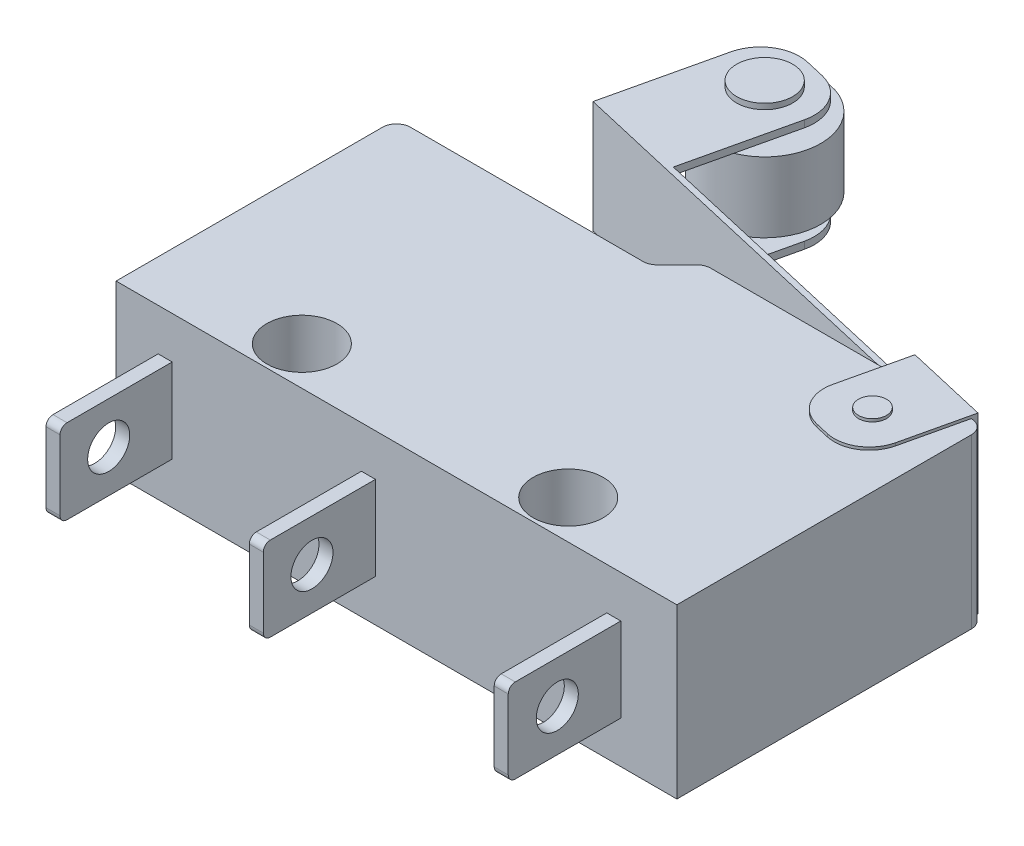
SolidWorks part; units mm, degrees
ref_plane "Ön Düzlem" through (0, 0, 0) normal (0, 0, 1) x (1, 0, 0)
ref_plane "Üst Düzlem" through (0, 0, 0) normal (0, 1, 0) x (1, 0, 0)
ref_plane "Sağ Düzlem" through (0, 0, 0) normal (1, 0, 0) x (0, 0, -1)
sketch "Çizim1" plane through (0, 0, 0) normal (0, 1, 0) x (1, 0, 0)
  line L0 (-10, 4.5) -> (10, 4.5) construction
  line L1 (0.2071, 5.5) -> (9.5, 5.5)
  line L2 (-10, 4) -> (-10, -5.5)
  line L3 (-10, -5.5) -> (10, -5.5)
  line L4 (10, 5) -> (10, -5.5)
  line L5 (-10, 5.5) -> (10, -5.5) construction
  line L6 (-10, -5.5) -> (10, 5.5) construction
  line L7 (0, 5.5) -> (0, -5.5) construction
  line L8 (-9.5, 4.5) -> (-1.2071, 4.5)
  line L9 (-0.8536, 4.6464) -> (-0.1464, 5.3536)
  line L10 (-10, -4.125) -> (10, -4.125) construction
  circle A0 centre (-4.75, -4.125) radius 1.25
  circle A1 centre (4.75, -4.125) radius 1.25
  arc A2 (9.5, 5.5) -> (10, 5) centre (9.5, 5) cw
  arc A3 (0.2071, 5.5) -> (-0.1464, 5.3536) centre (0.2071, 5) ccw
  arc A4 (-1.2071, 4.5) -> (-0.8536, 4.6464) centre (-1.2071, 5) ccw
  arc A5 (-10, 4) -> (-9.5, 4.5) centre (-9.5, 4) cw
  point P0 (0, 0)
  point P25 (-1, 4.5)
  dimension "D6" = 2.5
  dimension "D7" = 5.25
  dimension "D8" = 0.5
  dimension "D1" = 20
  dimension "D2" = 11
  dimension "D3" = 10
  dimension "D4" = 45
  dimension "D5" = 2.75
extrude "Yükseklik-Ekstrüzyon1" add sketch "Çizim1" along normal blind 3 and the other way blind 3
sketch "Çizim2" plane through (0, 0, -5.5) normal (0, 0, -1) x (-1, 0, 0)
  line L0 (-1.8536, 3) -> (-1.8536, -3) construction
  line L1 (-9.5, 3) -> (-0.2071, 3) construction
  line L2 (-9.5, -3) -> (-0.2071, -3) construction
  line L3 (0.1464, -3) -> (0.1464, 3) construction
  line L4 (-2.8536, 1) -> (-0.8536, 1)
  line L5 (-2.8536, 1) -> (-2.8536, -1)
  line L6 (-2.8536, -1) -> (-0.8536, -1)
  line L7 (-0.8536, 1) -> (-0.8536, -1)
  line L8 (-2.8536, 1) -> (-0.8536, -1) construction
  line L9 (-2.8536, -1) -> (-0.8536, 1) construction
  point P6 (-1.8536, 0)
  dimension "D1" = 2
  dimension "D2" = 2
  dimension "D3" = 2
extrude "Yükseklik-Ekstrüzyon2" add sketch "Çizim2" along normal blind 1.5
ref_plane "Düzlem1" through (0, 0, 0) normal (0, 1, 0) x (1, 0, 0)
sketch "Çizim3" plane through (0, 0, 0) normal (0, 1, 0) x (1, 0, 0)
  line L0 (9.5, 5.5) -> (-8.0387, 9.5491) construction
  line L10 (9.5, 5.5) -> (8.9939, 3.3077)
  line L11 (7.4947, 2.3709) -> (7.0075, 2.4834)
  line L12 (6.0707, 3.9825) -> (6.5769, 6.1749)
  line L13 (6.5769, 6.1749) -> (-8.0387, 9.5491)
  line L14 (-8.0387, 9.5491) -> (-7.1164, 13.544)
  line L15 (-5.4373, 14.5932) -> (-4.7553, 14.4358)
  line L16 (-3.7061, 12.7567) -> (-4.5834, 8.9567)
  line L17 (-4.5834, 8.9567) -> (9.545, 5.6949)
  line L19 (9.5, 5.5) -> (9.545, 5.6949)
  line L20 (9.5, 5.5) -> (0.2071, 5.5) construction
  arc A2 (-4.7553, 14.4358) -> (-3.7061, 12.7567) centre (-5.0702, 13.0716) cw
  arc A3 (-7.1164, 13.544) -> (-5.4373, 14.5932) centre (-5.7522, 13.2291) cw
  arc A4 (8.9939, 3.3077) -> (7.4947, 2.3709) centre (7.7759, 3.5889) cw
  arc A5 (7.0075, 2.4834) -> (6.0707, 3.9825) centre (7.2887, 3.7013) cw
  point P12 (-3.3911, 14.1208)
  point P15 (-6.8014, 14.9082)
  point P18 (8.7127, 2.0897)
  point P22 (5.7896, 2.7646)
  dimension "D6" = 5.5
  dimension "D10" = 1.4
  dimension "D11" = 1.25
  dimension "D1" = 18
  dimension "D2" = 90
  dimension "D3" = 3.5
  dimension "D4" = 3
  dimension "D5" = 90
  dimension "D7" = 3.5
  dimension "D8" = 90
  dimension "D9" = 5.3
  dimension "D12" = 13
extrude "Yükseklik-Ekstrüzyon6" add sketch "Çizim3" along normal blind 3.1 and the other way blind 3.1
sketch "Çizim4" plane through (1.7312, 0, -7.4988) normal (0.225, 0, -0.9744) x (-0.9744, 0, -0.225)
  line L0 (-5.0193, 3.1) -> (-5.0193, -3.1) construction
  line L1 (-5.0193, 2.5006) -> (-4.5193, 2.0006)
  line L2 (-8.0193, -3.1) -> (6.4807, -3.1) construction
  line L3 (-8.0193, -3.1) -> (-8.0193, 3.1) construction
  line L4 (-5.0193, 0) -> (6.4807, 0) construction
  line L5 (6.4807, -3.1) -> (6.4807, 3.1) construction
  line L6 (-5.0193, 3.1) -> (10.02, 3.1)
  line L7 (-5.0193, 3.1) -> (-5.0193, 2.5006)
  line L8 (-4.5193, 2.0006) -> (10.02, 2.0006)
  line L9 (10.02, 3.1) -> (10.02, 2.0006)
  line L10 (-4.5193, -2.0006) -> (10.02, -2.0006)
  line L11 (10.02, -3.1) -> (10.02, -2.0006)
  line L12 (-5.0193, -3.1) -> (10.02, -3.1)
  line L13 (-5.0193, -2.5006) -> (-4.5193, -2.0006)
  line L14 (-5.0193, -3.1) -> (-5.0193, -2.5006)
  point P2 (-5.0193, 2.0006)
  point P13 (-5.0193, 2.6)
  dimension "D1" = 3
  dimension "D2" = 1.0994
  dimension "D5" = 0.5
extrude "Kes-Ekstrüzyon1" cut sketch "Çizim4" against normal blind 0.5 and the other way blind 6
sketch "Çizim5" plane through (2.9235, 0, -12.663) normal (0.225, 0, -0.9744) x (-0.9744, 0, -0.225)
  line L0 (8.2307, 2.0006) -> (8.2307, -2.0006) construction
  line L1 (8.5807, 2.0006) -> (7.8807, 2.0006) construction
  line L2 (7.8807, -2.0006) -> (8.5807, -2.0006) construction
  line L3 (9.9807, 2.0006) -> (8.5807, 2.0006) construction
  line L4 (5.7307, 1.7506) -> (10.7307, 1.7506)
  line L5 (5.7307, 1.7506) -> (5.7307, -1.7506)
  line L6 (5.7307, -1.7506) -> (10.7307, -1.7506)
  line L7 (10.7307, 1.7506) -> (10.7307, -1.7506)
  line L8 (5.7307, 1.7506) -> (10.7307, -1.7506) construction
  line L9 (5.7307, -1.7506) -> (10.7307, 1.7506) construction
  point P6 (8.2307, 0)
  dimension "D1" = 0.25
  dimension "D2" = 5
extrude "Kes-Ekstrüzyon2" cut sketch "Çizim5" against normal blind 5.25
ref_plane "Düzlem2" through (0, 0.0006, 0) normal (0, 1, 0) x (1, 0, 0)
sketch "Çizim6" plane through (0, 0.0006, 0) normal (0, 1, 0) x (1, 0, 0)
  line L0 (-5.0963, 14.5145) -> (-6.3335, 9.1555) construction
  line L1 (-5.4373, 14.5932) -> (-4.7553, 14.4358) construction
  line L2 (6.0897, 6.2873) -> (-8.0387, 9.5491) construction
  circle A0 centre (-5.4313, 13.0633) radius 2
  dimension "D1" = 4
extrude "Yükseklik-Ekstrüzyon7" add sketch "Çizim6" along normal blind 1.25 and the other way blind 1.25 separate body
sketch "Çizim7" plane through (0, 0.0006, 0) normal (0, 1, 0) x (1, 0, 0)
  circle A0 centre (-5.4313, 13.0633) radius 1
  dimension "D1" = 2
extrude "Yükseklik-Ekstrüzyon8" add sketch "Çizim7" along normal blind 2.2 and the other way blind 2.2
ref_plane "Düzlem3" through (-8.25, 0, 0) normal (-1, 0, 0) x (0, 0, 1)
sketch "Çizim8" plane through (-8.25, 0, 0) normal (-1, 0, 0) x (0, 0, 1)
  line L0 (5.5, 3) -> (5.5, -3) construction
  line L1 (5.5, 1.5) -> (5.5, -1.5)
  line L2 (5.5, 1.5) -> (9.25, 1.5)
  line L4 (5.5, -1.5) -> (9.25, -1.5)
  line L5 (9.5, 1.25) -> (9.5, -1.25)
  line L6 (5.5, 0) -> (9.5, -1.5) construction
  line L7 (5.5, 0) -> (9.5, 1.5) construction
  arc A0 (9.25, -1.5) -> (9.5, -1.25) centre (9.25, -1.25) ccw
  arc A1 (9.25, 1.5) -> (9.5, 1.25) centre (9.25, 1.25) cw
  point P4 (5.5, 0)
  dimension "D1" = 0.25
  dimension "D2" = 3
extrude "Yükseklik-Ekstrüzyon9" add sketch "Çizim8" along normal blind 0.25 and the other way blind 0.25
ref_plane "Düzlem4" through (7.75, 0, 0) normal (1, 0, 0) x (0, 0, -1)
sketch "Çizim9" plane through (7.75, 0, 0) normal (1, 0, 0) x (0, 0, -1)
  line L1 (-5.5, 1.5) -> (-9.2642, 1.5)
  line L2 (-5.5, 1.5) -> (-5.5, -1.5)
  line L3 (-5.5, -1.5) -> (-9.2642, -1.5)
  line L4 (-9.5142, 1.25) -> (-9.5142, -1.25)
  arc A0 (-9.2642, -1.5) -> (-9.5142, -1.25) centre (-9.2642, -1.25) cw
  arc A1 (-9.2642, 1.5) -> (-9.5142, 1.25) centre (-9.2642, 1.25) ccw
  dimension "D1" = 0.25
extrude "Yükseklik-Ekstrüzyon10" add sketch "Çizim9" along normal blind 0.25 and the other way blind 0.25
ref_plane "Düzlem5" through (-1, 0, 0) normal (1, 0, 0) x (0, 0, -1)
sketch "Çizim10" plane through (-1, 0, 0) normal (1, 0, 0) x (0, 0, -1)
  line L1 (-5.5, 1.5) -> (-9.25, 1.5)
  line L2 (-5.5, 1.5) -> (-5.5, -1.5)
  line L3 (-5.5, -1.5) -> (-9.25, -1.5)
  line L4 (-9.5, 1.25) -> (-9.5, -1.25)
  arc A0 (-9.25, -1.5) -> (-9.5, -1.25) centre (-9.25, -1.25) cw
  arc A1 (-9.25, 1.5) -> (-9.5, 1.25) centre (-9.25, 1.25) ccw
  point P9 (-9.5, 1.5)
  dimension "D2" = 0.25
  dimension "D1" = 4
extrude "Yükseklik-Ekstrüzyon11" add sketch "Çizim10" along normal blind 0.25 and the other way blind 0.25
sketch "Çizim11" plane through (8, 0, 0) normal (1, 0, 0) x (0, 0, -1)
  line L0 (-7.7642, 1.5) -> (-7.7642, -1.5) construction
  line L1 (-5.5, 1.5) -> (-9.2642, 1.5) construction
  line L2 (-9.2642, -1.5) -> (-5.5, -1.5) construction
  line L3 (-9.5142, 1.25) -> (-9.5142, -1.25) construction
  circle A0 centre (-7.7642, 0) radius 0.75
  dimension "D2" = 1.5
  dimension "D1" = 1.75
extrude "Kes-Ekstrüzyon3" cut sketch "Çizim11" against normal up to surface (18 mm away) up to face at (-10, 0, 0.75)
ref_plane "Düzlem6" through (0, 0, 0) normal (0, 1, 0) x (1, 0, 0)
sketch "Çizim13" plane through (0, 0, 0) normal (0, 1, 0) x (1, 0, 0)
  line L0 (7.2511, 2.4271) -> (8.0834, 6.0323) construction
  line L1 (7.4947, 2.3709) -> (7.0075, 2.4834) construction
  line L2 (9.545, 5.6949) -> (6.6219, 6.3697) construction
  circle A0 centre (7.5885, 3.8887) radius 0.5
  dimension "D1" = 1
  dimension "D2" = 1.5
extrude "Yükseklik-Ekstrüzyon13" add sketch "Çizim13" along normal blind 3.2 and the other way blind 3.2
